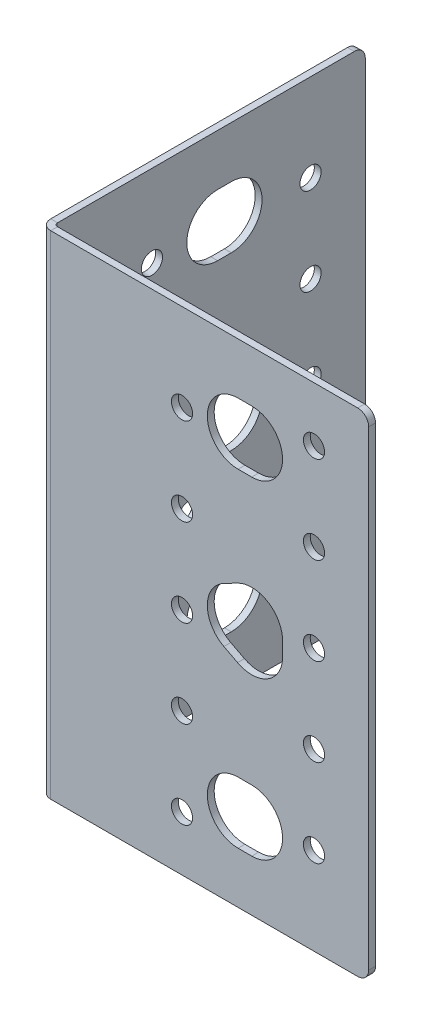
SolidWorks part; units mm, degrees
note: The reader was unsure of these and kept them because the rebuilt part matched: flange length of "Edge-Flange1".
material "5052-H32"
ref_plane "Front Plane" through (0, 0, 0) normal (0, 0, 1) x (1, 0, 0)
ref_plane "Top Plane" through (0, 0, 0) normal (0, 1, 0) x (1, 0, 0)
ref_plane "Right Plane" through (0, 0, 0) normal (1, 0, 0) x (0, 0, -1)
sketch "Sketch1" plane through (0, 0, 0) normal (0, 0, 1) x (1, 0, 0)
  line L1 (0, 0) -> (73.8188, 0)
  line L2 (0, 0) -> (0, 114.3)
  line L3 (0, 114.3) -> (73.8188, 114.3)
  line L4 (73.8188, 0) -> (73.8188, 114.3)
  line L5 (0, 0) -> (73.8188, 114.3) construction
  line L6 (0, 114.3) -> (73.8188, 0) construction
  point P4 (36.9094, 57.15)
  dimension "D1" = 114.3
  dimension "D2" = 73.8188
base flange "Base-Flange1" sketch "Sketch1" thickness 1.5875 reverse thickness direction no parameters "D1"=10
edge flange "Edge-Flange1" sketch "Sketch10" flange angle 90 flange length 73.8188 flange position bend outside bend radius 0.7937 thickness 1.5875 relief rectangular parameters "D6"=10
sketch "Sketch10" plane through (0, 0, -1.5875) normal (-1, 0, 0) x (0, 1, 0)
  line L0 (114.3, 0) -> (0, 0) construction
  line L1 (114.3, 0) -> (0, 0)
  line L2 (0, 0) -> (0, 72.2313)
  line L3 (0, 72.2313) -> (114.3, 72.2313)
  line L4 (114.3, 72.2313) -> (114.3, 0)
bend "EdgeBend1" bend radius 0.7937 bend angle 90 parameters "D5"=1
sketch "Sketch11" plane through (0, 0, 0) normal (0, 0, 1) x (1, 0, 0)
  line L0 (0, 0) -> (73.8188, 0) construction
  line L1 (0, 114.3) -> (0, 0) construction
  line L2 (46.6789, 114.3) -> (46.6789, 95.25) construction
  line L3 (46.6789, 95.25) -> (46.6789, 58.801) construction
  line L4 (73.8188, 114.3) -> (0, 114.3) construction
  line L5 (73.8188, 0) -> (73.8188, 114.3) construction
  line L6 (46.6789, 58.801) -> (46.6789, 55.499) construction
  line L7 (46.6789, 19.05) -> (46.6789, 0) construction
  line L8 (46.6789, 55.499) -> (46.6789, 19.05) construction
  line L9 (46.6789, 58.801) -> (46.6789, 55.499) construction
  line L10 (53.8226, 58.801) -> (53.8226, 55.499) construction
  line L11 (39.5351, 58.801) -> (39.5351, 55.499) construction
  line L12 (43.5039, 114.3) -> (43.5039, 0) construction
  line L13 (46.6789, 95.25) -> (43.5039, 95.25) construction
  line L14 (46.6789, 88.1063) -> (43.5039, 88.1063)
  line L15 (46.6789, 102.3937) -> (43.5039, 102.3937)
  line L16 (46.6789, 19.05) -> (43.5039, 19.05) construction
  line L17 (46.6789, 11.9063) -> (43.5039, 11.9063)
  line L18 (46.6789, 26.1938) -> (43.5039, 26.1938)
  line L19 (43.3831, 65.1391) -> (40.2081, 63.4881)
  line L20 (40.2081, 50.8119) -> (43.3831, 49.1609)
  line L21 (53.8226, 55.499) -> (53.8226, 58.801)
  circle A0 centre (30.48, 12.7) radius 2.4575
  circle A1 centre (30.48, 33.02) radius 2.4575
  circle A2 centre (30.48, 53.34) radius 2.4575
  circle A3 centre (30.48, 73.66) radius 2.4574
  circle A4 centre (30.48, 93.98) radius 2.4574
  circle A6 centre (61.1187, 101.6) radius 2.4574
  circle A7 centre (61.1188, 81.28) radius 2.4574
  circle A8 centre (61.1188, 60.96) radius 2.4575
  circle A9 centre (61.1188, 40.64) radius 2.4575
  circle A10 centre (61.1188, 20.32) radius 2.4575
  circle A11 centre (46.6789, 95.25) radius 7.1437 construction
  circle A12 centre (46.6789, 19.05) radius 7.1437 construction
  arc A13 (53.8226, 58.801) -> (39.5351, 58.801) centre (46.6789, 58.801) ccw construction
  arc A14 (39.5351, 55.499) -> (53.8226, 55.499) centre (46.6789, 55.499) ccw construction
  arc A15 (46.6789, 88.1063) -> (46.6789, 102.3937) centre (46.6789, 95.25) ccw
  arc A16 (43.5039, 102.3937) -> (43.5039, 88.1063) centre (43.5039, 95.25) ccw
  arc A17 (46.6789, 11.9063) -> (46.6789, 26.1938) centre (46.6789, 19.05) ccw
  arc A18 (43.5039, 26.1938) -> (43.5039, 11.9063) centre (43.5039, 19.05) ccw
  circle A19 centre (43.5039, 57.15) radius 7.1437 construction
  arc A20 (40.2081, 63.4881) -> (40.2081, 50.8119) centre (43.5039, 57.15) ccw
  arc A21 (43.3831, 49.1609) -> (53.8226, 55.499) centre (46.6789, 55.499) ccw
  arc A22 (43.3831, 65.1391) -> (53.8226, 58.801) centre (46.6789, 58.801) cw
  point P35 (46.6789, 57.15)
  point P43 (45.0914, 95.25)
  point P49 (45.0914, 19.05)
  dimension "D1" = 12.7
  dimension "D2" = 30.48
  dimension "D3" = 4.9149
  dimension "D4" = 5
  dimension "D5" = 12.7
  dimension "D6" = 12.7
  dimension "D13" = 14.2875
  dimension "D8" = 20.32
  dimension "D9" = 20.32
  dimension "D10" = 27.1399
  dimension "D11" = 19.05
  dimension "D12" = 36.449
  dimension "D14" = 3.175
  dimension "D7" = 5
extrude "Cut-Extrude1" cut sketch "Sketch11" against normal through all normal cut yes
sketch "Sketch12" plane through (-2.3812, 0, 0) normal (-1, 0, 0) x (0, 0, 1)
  line L0 (-42.7101, 114.3) -> (-42.7101, 95.25) construction
  line L1 (-2.3813, 114.3) -> (-73.8188, 114.3) construction
  line L2 (-24.2951, 114.3) -> (-24.2951, 95.25) construction
  line L3 (-73.8188, 114.3) -> (-73.8188, 0) construction
  line L4 (-32.8612, 73.66) -> (-32.8612, 114.3) construction
  line L5 (-61.1188, 12.7) -> (-61.1188, 33.02) construction
  line L6 (-73.8188, 0) -> (-2.3812, 0) construction
  line L7 (-42.7101, 95.25) -> (-42.7101, 58.801) construction
  line L8 (-42.7101, 58.801) -> (-42.7101, 55.499) construction
  line L9 (-42.7101, 19.05) -> (-42.7101, 0) construction
  line L10 (-42.7101, 55.499) -> (-42.7101, 19.05) construction
  line L13 (-42.7101, 58.801) -> (-42.7101, 55.499) construction
  line L14 (-35.5664, 58.801) -> (-35.5664, 55.499)
  line L15 (-49.8539, 58.801) -> (-49.8539, 55.499)
  line L16 (-42.7101, 95.25) -> (-39.5351, 95.25) construction
  line L17 (-42.7101, 102.3938) -> (-39.5351, 102.3938)
  line L18 (-42.7101, 88.1063) -> (-39.5351, 88.1063)
  line L19 (-42.7101, 19.05) -> (-39.5351, 19.05) construction
  line L20 (-42.7101, 26.1937) -> (-39.5351, 26.1937)
  line L21 (-42.7101, 11.9062) -> (-39.5351, 11.9062)
  line L22 (-32.8612, 40.64) -> (-32.8612, 0) construction
  line L23 (-2.3813, 114.3) -> (-2.3812, 0) construction
  line L24 (-24.2951, 95.25) -> (-24.2951, 19.05) construction
  line L25 (-24.2951, 19.05) -> (-24.2951, 0) construction
  circle A0 centre (-61.1188, 12.7) radius 2.4574
  circle A14 centre (-61.1188, 33.02) radius 2.4575
  circle A15 centre (-61.1188, 53.34) radius 2.4575
  circle A16 centre (-61.1188, 73.66) radius 2.4574
  circle A17 centre (-61.1188, 93.98) radius 2.4574
  circle A18 centre (-42.7101, 95.25) radius 7.1437 construction
  circle A20 centre (-42.7101, 19.05) radius 7.1437 construction
  arc A23 (-35.5664, 58.801) -> (-49.8539, 58.801) centre (-42.7101, 58.801) ccw
  arc A24 (-49.8539, 55.499) -> (-35.5664, 55.499) centre (-42.7101, 55.499) ccw
  circle A26 centre (-32.8612, 73.66) radius 2.4574
  circle A27 centre (-32.8612, 40.64) radius 2.4575
  arc A31 (-42.7101, 102.3938) -> (-42.7101, 88.1063) centre (-42.7101, 95.25) ccw
  arc A32 (-39.5351, 88.1063) -> (-39.5351, 102.3938) centre (-39.5351, 95.25) ccw
  arc A33 (-42.7101, 26.1937) -> (-42.7101, 11.9062) centre (-42.7101, 19.05) ccw
  arc A34 (-39.5351, 11.9062) -> (-39.5351, 26.1937) centre (-39.5351, 19.05) ccw
  circle A35 centre (-24.2951, 95.25) radius 2.4574
  circle A36 centre (-24.2951, 19.05) radius 2.4574
  point P7 (-41.1226, 95.25)
  point P38 (-42.7101, 57.15)
  point P53 (-41.1226, 19.05)
  dimension "D1" = 4.9149
  dimension "D4" = 12.7
  dimension "D12" = 36.449
  dimension "D13" = 14.2875
  dimension "D3" = 30.48
  dimension "D5" = 15.24
  dimension "D2" = 40.64
  dimension "D7" = 12.7
  dimension "D9" = 20.32
  dimension "D10" = 31.1086
  dimension "D11" = 19.05
  dimension "D14" = 3.175
  dimension "D8" = 5
extrude "Cut-Extrude2" cut sketch "Sketch12" against normal through all normal cut yes
fillet "Fillet1" radius 2.54 4 edges at (73.8188, 114.3, -0.7937) (73.8188, 0, -0.7937) (-1.5875, 0, -73.8188) (-1.5875, 114.3, -73.8188)
sketch "Bend-Lines1" [suppressed] plane through (0, 0, 0) normal (0, 1, 0) x (1, 0, 0)
sketch "Bounding-Box1" [suppressed] plane through (0, 0, 0) normal (0, 1, 0) x (1, 0, 0)
sheet metal parameters "Sheet-Metal1" thickness 1.5875 parameters "D1"=10
flat pattern "Flat-Pattern1" [suppressed]
sketch "Bend-Lines2" plane through (0, 0, 0) normal (0, 1, 0) x (1, 0, 0)
sketch3d "Bounding-Box2" [suppressed]
  line L0 (74.6125, 114.3, 0) -> (74.6125, 0, 0) construction
  line L1 (0, 114.3, 0) -> (0, 0, 0) construction
  line L2 (74.6125, 114.3, 0) -> (0, 114.3, 0) construction
  line L3 (74.6125, 0, 0) -> (0, 0, 0) construction
sheet metal parameters "Sheet-Metal2" thickness 1.5875 parameters "D1"=10
flat pattern "Flat-Pattern1"
sketch "Bend-Lines2" plane through (0, 0, 0) normal (0, 0, 1) x (1, 0, 0)
  line L0 (-0.9975, 114.3) -> (-0.9975, 0) construction
  line L1 (-0.9975, 114.3) -> (-0.9975, 0) construction
sketch3d "Bounding-Box2" [suppressed]
  line L0 (-73.4324, 0, 0) -> (73.8188, 0, 0) construction
  line L1 (-73.4324, 114.3, 0) -> (73.8188, 114.3, 0) construction
  line L2 (-73.4324, 0, 0) -> (-73.4324, 114.3, 0) construction
  line L3 (73.8188, 0, 0) -> (73.8188, 114.3, 0) construction
bend of the flat pattern "Flatten-<EdgeBend1>1"
sheet metal parameters "Sheet-Metal3" thickness 1.5875 parameters "D1"=10
flat pattern "Flat-Pattern1"
sketch "Bend-Lines2" plane through (0, 0, 0) normal (0, 0, 1) x (1, 0, 0)
  line L0 (-0.9975, 114.3) -> (-0.9975, 0) construction
  line L1 (-0.9975, 114.3) -> (-0.9975, 0) construction
sketch3d "Bounding-Box2" [suppressed]
  line L0 (-73.4324, 0, 0) -> (73.8188, 0, 0) construction
  line L1 (-73.4324, 114.3, 0) -> (73.8188, 114.3, 0) construction
  line L2 (-73.4324, 0, 0) -> (-73.4324, 114.3, 0) construction
  line L3 (73.8188, 0, 0) -> (73.8188, 114.3, 0) construction
bend of the flat pattern "Flatten-<EdgeBend1>1"
sheet metal parameters "Sheet-Metal4" thickness 1.5875 parameters "D1"=10
flat pattern "Flat-Pattern1"
sketch "Bend-Lines2" plane through (0, 0, 0) normal (0, 0, 1) x (1, 0, 0)
  line L0 (-0.9975, 114.3) -> (-0.9975, 0) construction
  line L1 (-0.9975, 114.3) -> (-0.9975, 0) construction
sketch3d "Bounding-Box2" [suppressed]
  line L0 (-73.4324, 0, 0) -> (73.8188, 0, 0) construction
  line L1 (-73.4324, 114.3, 0) -> (73.8188, 114.3, 0) construction
  line L2 (-73.4324, 0, 0) -> (-73.4324, 114.3, 0) construction
  line L3 (73.8188, 0, 0) -> (73.8188, 114.3, 0) construction
bend of the flat pattern "Flatten-<EdgeBend1>1"
